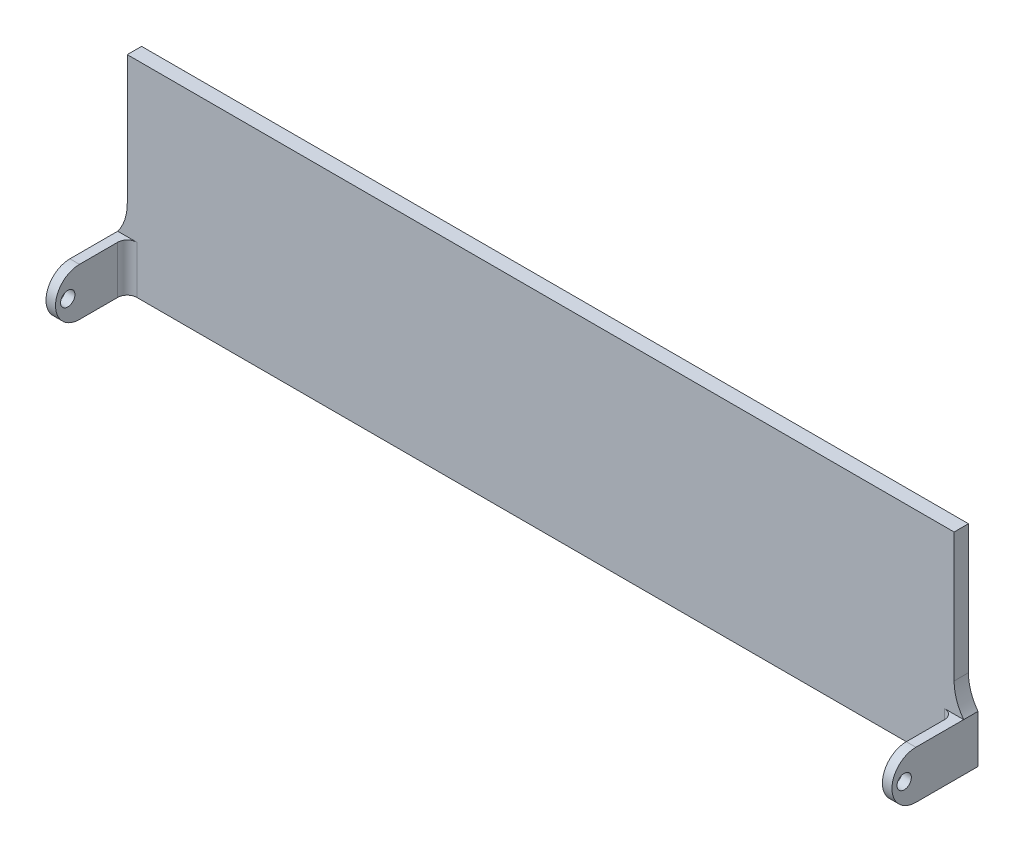
SolidWorks part; units mm, degrees
ref_plane "Front Plane" through (0, 0, 0) normal (0, 0, 1) x (1, 0, 0)
ref_plane "Top Plane" through (0, 0, 0) normal (0, 1, 0) x (1, 0, 0)
ref_plane "Right Plane" through (0, 0, 0) normal (1, 0, 0) x (0, 0, -1)
sketch "Sketch1" plane through (0, 0, 0) normal (0, 0, 1) x (1, 0, 0)
  line L1 (-86.5, -21.5) -> (86.5, -21.5)
  line L2 (-86.5, -21.5) -> (-86.5, 21.5)
  line L3 (-86.5, 21.5) -> (86.5, 21.5)
  line L4 (86.5, -21.5) -> (86.5, 21.5)
  line L5 (-86.5, -21.5) -> (86.5, 21.5) construction
  line L6 (-86.5, 21.5) -> (86.5, -21.5) construction
  point P0 (0, 0)
  dimension "D1" = 173
  dimension "D2" = 43
extrude "Boss-Extrude1" add sketch "Sketch1" along normal blind 3
sketch "Sketch2" plane through (-86.5, 0, 0) normal (-1, 0, 0) x (0, 0, 1)
  line L0 (3, 21.5) -> (3, -21.5) construction
  line L1 (0, -21.5) -> (13, -21.5)
  line L2 (0, -21.5) -> (0, -11.5)
  line L3 (0, -11.5) -> (13, -11.5)
  line L4 (13, -21.5) -> (13, -11.5)
  circle A0 centre (13, -16.5) radius 5
  dimension "D1" = 10
  dimension "D2" = 10
extrude "Boss-Extrude2" add sketch "Sketch2" along normal blind 2 contours L2 L1 L4 L3 | A0
sketch "Sketch3" plane through (86.5, 0, 0) normal (1, 0, 0) x (0, 0, -1)
  line L1 (0, -21.5) -> (-13, -21.5)
  line L2 (0, -21.5) -> (0, -11.5)
  line L3 (0, -11.5) -> (-13, -11.5)
  line L4 (-13, -21.5) -> (-13, -11.5)
  circle A0 centre (-13, -16.5) radius 5
extrude "Boss-Extrude3" add sketch "Sketch3" along normal blind 2 contours L2 L1 L4 L3 | A0
sketch "Sketch4" plane through (88.5, 0, 0) normal (1, 0, 0) x (0, 0, -1)
  circle A0 centre (-15.4465, -16.5) radius 1.5
  dimension "D1" = 3
extrude "Cut-Extrude1" cut sketch "Sketch4" against normal blind 200
fillet "Fillet1" radius 10 2 edges at (-86.5, -11.5, 1.5) (86.5, -11.5, 1.5)
fillet "Fillet2" radius 2 2 edges at (86.5, -16.5, 3) (-86.5, -16.5, 3)
